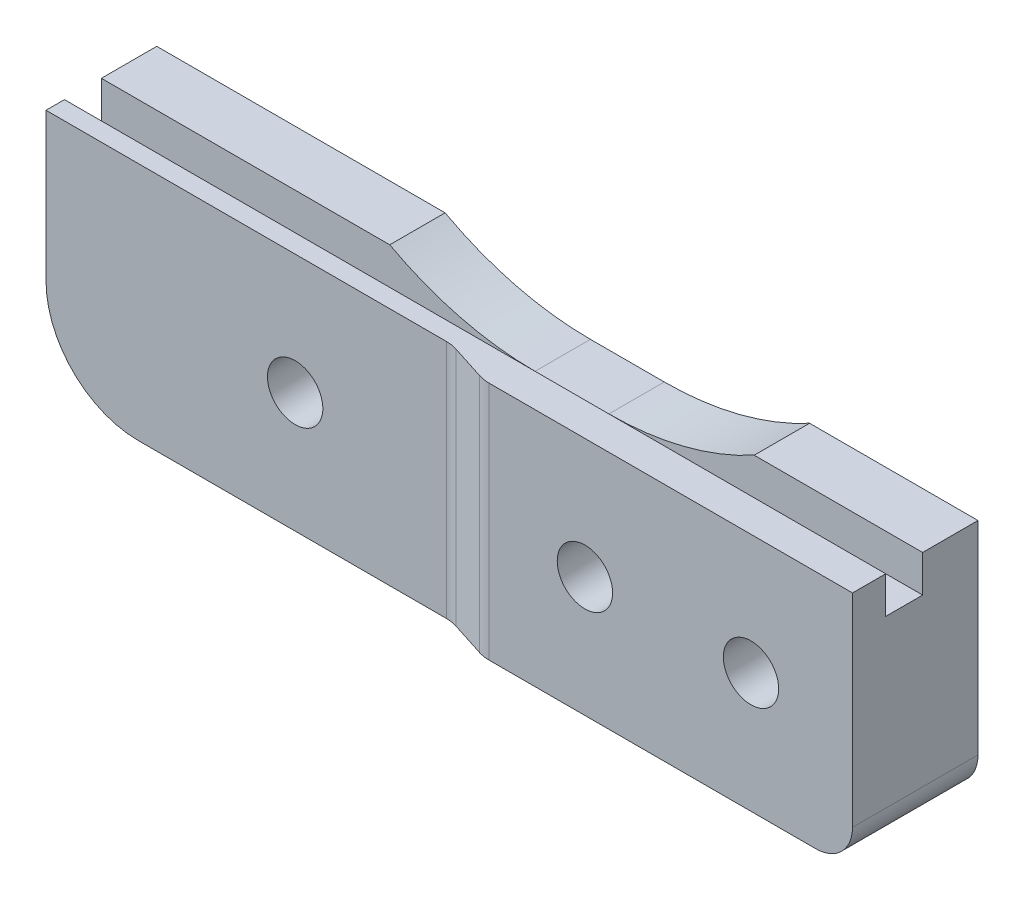
SolidWorks part; units mm, degrees
material "ABS"
ref_plane "Front" through (0, 0, 0) normal (0, 0, 1) x (1, 0, 0)
ref_plane "Top" through (0, 0, 0) normal (0, 1, 0) x (1, 0, 0)
ref_plane "Right" through (0, 0, 0) normal (1, 0, 0) x (0, 0, -1)
sketch "Esquisse1" plane through (0, 0, 0) normal (0, 0, 1) x (1, 0, 0)
  line L1 (0, 0) -> (44.5, 0)
  line L2 (0, 0) -> (0, 13)
  line L3 (0, 13) -> (44.5, 13)
  line L4 (44.5, 0) -> (44.5, 13)
  dimension "D1" = 13
  dimension "D2" = 44.5
extrude "Boss.-Extru.1" add sketch "Esquisse1" along normal blind 6
sketch "Esquisse2" plane through (44.5, 0, 0) normal (1, 0, 0) x (0, 0, -1)
  line L0 (-6, 13) -> (0, 13) construction
  line L1 (-5, 11) -> (-3, 11)
  line L2 (-5, 11) -> (-5, 13)
  line L3 (-5, 13) -> (-3, 13)
  line L4 (-3, 11) -> (-3, 13)
  line L5 (-6, 0) -> (-6, 13) construction
  dimension "D1" = 1
  dimension "D2" = 2
  dimension "D3" = 2
extrude "Enlèv. mat.-Extru.1" cut sketch "Esquisse2" against normal through all
sketch "Esquisse4" plane through (0, 0, 0) normal (0, -1, 0) x (1, 0, 0)
  line L0 (0, 6) -> (0, 0) construction
  line L1 (44.5, 6) -> (22, 6)
  line L2 (44.5, 6) -> (44.5, 6.8)
  line L3 (44.5, 6.8) -> (24.5, 6.8)
  line L4 (22, 6) -> (24.5, 6.8)
  dimension "D1" = 0.8
  dimension "D2" = 22
  dimension "D3" = 20
extrude "Boss.-Extru.2" add sketch "Esquisse4" against normal up to surface (13 mm away) up to face at (22.25, 13, 5.5)
sketch "Esquisse3" plane through (0, 0, 0) normal (0, 0, 1) x (1, 0, 0)
  line L0 (0, 13) -> (0, 0) construction
  line L2 (22, 13) -> (0, 13) construction
  circle A0 centre (13.5, 6.5) radius 1.5
  circle A1 centre (30, 6.5) radius 1.5
  circle A2 centre (39, 6.5) radius 1.5
  dimension "D1" = 9
  dimension "D2" = 16.5
  dimension "D3" = 13.5
  dimension "D4" = 6.5
  dimension "D5" = 3
extrude "Enlèv. mat.-Extru.2" cut sketch "Esquisse3" along normal through all
sketch "Esquisse5" plane through (0, 0, 0) normal (0, 0, -1) x (-1, 0, 0)
  line L1 (-10.75, 8.0877) -> (-13.5, 9.6754)
  line L2 (-13.5, 9.6754) -> (-16.25, 8.0877)
  line L3 (-16.25, 8.0877) -> (-16.25, 4.9123)
  line L4 (-16.25, 4.9123) -> (-13.5, 3.3246)
  line L5 (-13.5, 3.3246) -> (-10.75, 4.9123)
  line L6 (-10.75, 4.9123) -> (-10.75, 8.0877)
  circle A0 centre (-13.5, 6.5) radius 2.75 construction
  circle A1 centre (-30, 6.5) radius 3
  circle A2 centre (-39, 6.5) radius 3
  dimension "D1" = 5.5
  dimension "D2" = 6
extrude "Enlèv. mat.-Extru.3" cut sketch "Esquisse5" against normal blind 3
fillet "Congé1" radius 5 1 edges at (0, 0, 3)
fillet "Congé2" radius 2 3 edges at (44.5, 0, 3.4) (24.5, 6.5, 6.8) (22, 6.5, 6)
sketch "Esquisse6" plane through (0, 0, 0) normal (0, 0, 1) x (1, 0, 0)
  line L0 (23.5, 27.5) -> (27.5, 27.5) construction
  line L1 (23.5, 44) -> (27.5, 44)
  line L2 (23.5, 11) -> (27.5, 11)
  arc A0 (23.5, 44) -> (23.5, 11) centre (23.5, 27.5) ccw
  arc A1 (27.5, 11) -> (27.5, 44) centre (27.5, 27.5) ccw
  circle A2 centre (13.5, 6.5) radius 1.5 construction
  point P2 (25.5, 27.5)
  dimension "D1" = 21
  dimension "D2" = 12
  dimension "D3" = 33
  dimension "D4" = 4
extrude "Enlèv. mat.-Extru.4" cut sketch "Esquisse6" along normal up to surface (5 mm away) up to face at (22.25, 12, 5)
